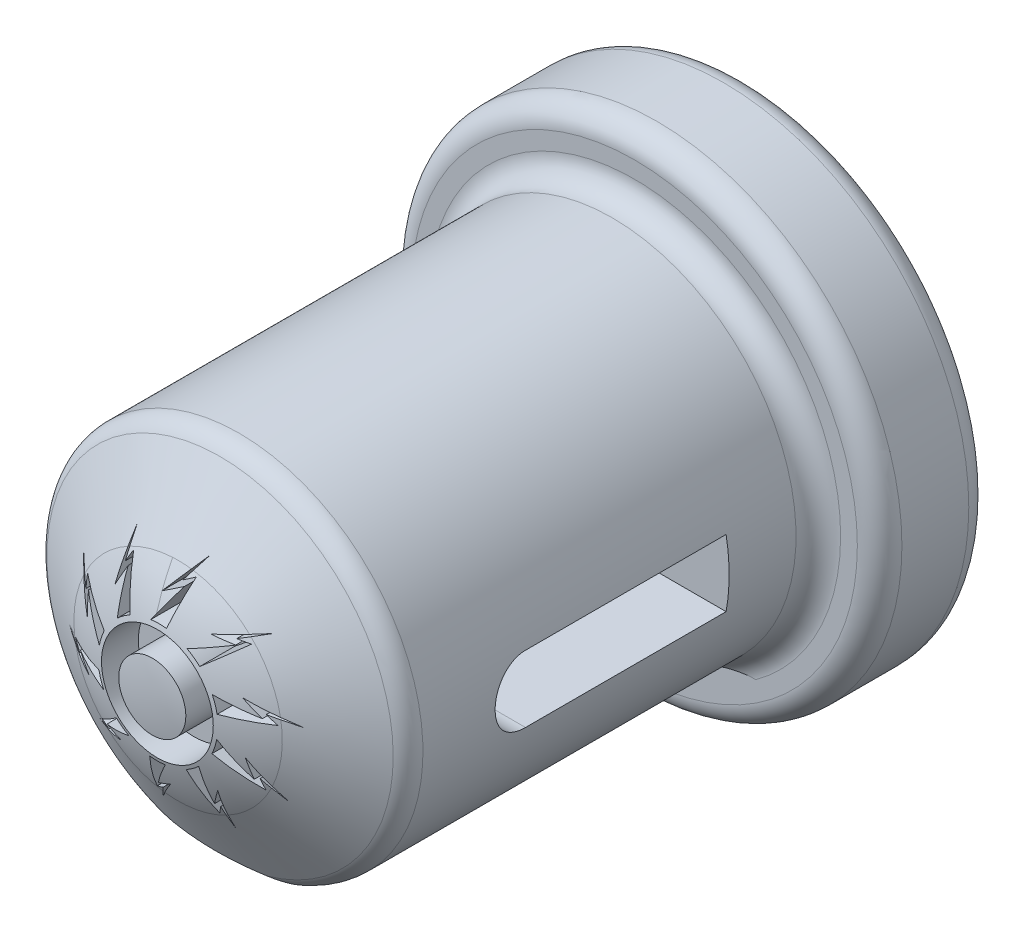
SolidWorks part; units mm, degrees
ref_plane "Alzado" through (0, 0, 0) normal (0, 0, 1) x (1, 0, 0)
ref_plane "Planta" through (0, 0, 0) normal (0, 1, 0) x (1, 0, 0)
ref_plane "Vista lateral" through (0, 0, 0) normal (1, 0, 0) x (0, 0, -1)
sketch "Croquis1" plane through (0, 0, 0) normal (0, 0, 1) x (1, 0, 0)
  line L0 (3.4971, -7.4721) -> (-3.4971, -7.4721)
  line L1 (2.75, -4.4721) -> (-2.75, -4.4721)
  arc A0 (2.75, -4.4721) -> (-2.75, -4.4721) centre (0, 0) ccw
  arc A1 (3.4971, -7.4721) -> (-3.4971, -7.4721) centre (0, 0) ccw
  point P7 (0, -4.4721)
  dimension "D1" = 10.5
  dimension "D2" = 5.5
  dimension "D3" = 3
extrude "Saliente-Extruir1" add sketch "Croquis1" along normal blind 23.3
sketch "Croquis2" plane through (0, 0, 0) normal (0, 0, -1) x (-1, 0, 0)
  line L0 (2.75, -4.4721) -> (-2.75, -4.4721) construction
  line L1 (2.75, -4.4721) -> (-2.75, -4.4721)
  circle A0 centre (0, 0) radius 11
  arc A1 (2.75, -4.4721) -> (-2.75, -4.4721) centre (0, 0) ccw construction
  arc A2 (2.75, -4.4721) -> (-2.75, -4.4721) centre (0, 0) ccw
  dimension "D1" = 22
extrude "Saliente-Extruir2" add sketch "Croquis2" against normal blind 5
sketch "Croquis3" plane through (0, 0, 0) normal (1, 0, 0) x (0, 0, -1)
  line L0 (-23.3, 0) -> (-23.3, 8.25)
  line L2 (-23.3, 8.25) -> (-25.4732, 4.6757)
  line L3 (-26.7831, 0) -> (-23.3, 0)
  arc A0 (-25.4732, 4.6757) -> (-26.7831, 0) centre (-17.7831, 0) ccw
  dimension "D2" = 9
  dimension "D1" = 31.3
revolve "Revolución1" add sketch "Croquis3" angle 360 about L3
sketch "Croquis4" plane through (0, 0, 23.3) normal (0, 0, -1) x (-1, 0, 0)
  line L1 (3.4971, -7.4721) -> (-3.4971, -7.4721)
  line L2 (3.4971, -7.4721) -> (-3.4971, -7.4721)
  arc A1 (-3.4971, -7.4721) -> (3.4971, -7.4721) centre (0, 0) ccw
  arc A2 (-3.4971, -7.4721) -> (3.4971, -7.4721) centre (0, 0) ccw
  dimension "D1" = 0
extrude "Cortar-Extruir1" cut sketch "Croquis4" against normal up to next
fillet "Redondeo3" radius 1 4 edges at (-11, 0, 0) (-11, 0, 5) (0, 8.25, 5) (0, 8.25, 23.3)
fillet "Redondeo2" radius 1 2 edges at (0, -4.4721, 0) (0, 5.25, 0)
ref_plane "Plano1" through (0, 0, 26.7831) normal (0, 0, 1) x (1, 0, 0)
sketch "Croquis5" plane through (0, 0, 26.7831) normal (0, 0, 1) x (1, 0, 0)
  line L0 (1.3026, 2.3441) -> (2.8816, 2.9738)
  line L1 (-0.324, 2.662) -> (0.5833, 4.0996)
  line L2 (0.5833, 4.0996) -> (-0.19, 3.662)
  line L3 (-0.19, 3.662) -> (1.0396, 5.192)
  line L4 (1.0396, 5.192) -> (0.4463, 4.2519)
  line L5 (0.4463, 4.2519) -> (0.876, 4.4951)
  line L6 (0.876, 4.4951) -> (0.376, 2.662)
  line L7 (2.8816, 2.9738) -> (1.9987, 3.0743)
  line L8 (1.9987, 3.0743) -> (3.8929, 3.5894)
  line L9 (3.8929, 3.5894) -> (2.8603, 3.1775)
  line L10 (2.8603, 3.1775) -> (3.3508, 3.1217)
  line L11 (3.3508, 3.1217) -> (1.8689, 1.9326)
  line L12 (2.4316, 1.1308) -> (4.0792, 0.7121)
  line L13 (4.0792, 0.7121) -> (3.4241, 1.3124)
  line L14 (3.4241, 1.3124) -> (5.2592, 0.6157)
  line L15 (5.2592, 0.6157) -> (4.1817, 0.8895)
  line L16 (4.1817, 0.8895) -> (4.5457, 0.5559)
  line L17 (4.5457, 0.5559) -> (2.6479, 0.465)
  line L18 (2.6319, -0.5144) -> (3.7187, -1.8216)
  line L19 (3.7187, -1.8216) -> (3.5415, -0.9509)
  line L20 (3.5415, -0.9509) -> (4.6166, -2.5932)
  line L21 (4.6166, -2.5932) -> (3.9059, -1.7384)
  line L22 (3.9059, -1.7384) -> (4.0044, -2.2222)
  line L23 (4.0044, -2.2222) -> (2.4155, -1.1802)
  line L24 (1.8268, -1.9632) -> (1.9378, -3.6595)
  line L25 (1.9378, -3.6595) -> (2.3062, -2.8509)
  line L26 (2.3062, -2.8509) -> (2.2107, -4.8115)
  line L27 (2.2107, -4.8115) -> (2.1381, -3.7022)
  line L28 (2.1381, -3.7022) -> (1.9334, -4.1515)
  line L29 (1.9334, -4.1515) -> (1.2605, -2.3746)
  line L30 (0.324, -2.662) -> (-0.5833, -4.0996)
  line L31 (-0.5833, -4.0996) -> (0.19, -3.662)
  line L32 (0.19, -3.662) -> (-1.0396, -5.192)
  line L33 (-1.0396, -5.192) -> (-0.4463, -4.2519)
  line L34 (-0.4463, -4.2519) -> (-0.876, -4.4951)
  line L35 (-0.876, -4.4951) -> (-0.376, -2.662)
  line L36 (-1.3026, -2.3441) -> (-2.8816, -2.9738)
  line L37 (-2.8816, -2.9738) -> (-1.9987, -3.0743)
  line L38 (-1.9987, -3.0743) -> (-3.8929, -3.5894)
  line L39 (-3.8929, -3.5894) -> (-2.8603, -3.1775)
  line L40 (-2.8603, -3.1775) -> (-3.3508, -3.1217)
  line L41 (-3.3508, -3.1217) -> (-1.8689, -1.9326)
  line L42 (-2.4316, -1.1308) -> (-4.0792, -0.7121)
  line L43 (-4.0792, -0.7121) -> (-3.4241, -1.3124)
  line L44 (-3.4241, -1.3124) -> (-5.2592, -0.6157)
  line L45 (-5.2592, -0.6157) -> (-4.1817, -0.8895)
  line L46 (-4.1817, -0.8895) -> (-4.5457, -0.5559)
  line L47 (-4.5457, -0.5559) -> (-2.6479, -0.465)
  line L48 (-2.6319, 0.5144) -> (-3.7187, 1.8216)
  line L49 (-3.7187, 1.8216) -> (-3.5415, 0.9509)
  line L50 (-3.5415, 0.9509) -> (-4.6166, 2.5932)
  line L51 (-4.6166, 2.5932) -> (-3.9059, 1.7384)
  line L52 (-3.9059, 1.7384) -> (-4.0044, 2.2222)
  line L53 (-4.0044, 2.2222) -> (-2.4155, 1.1802)
  line L54 (-1.8268, 1.9632) -> (-1.9378, 3.6595)
  line L55 (-1.9378, 3.6595) -> (-2.3062, 2.8509)
  line L56 (-2.3062, 2.8509) -> (-2.2107, 4.8115)
  line L57 (-2.2107, 4.8115) -> (-2.1381, 3.7022)
  line L58 (-2.1381, 3.7022) -> (-1.9334, 4.1515)
  line L59 (-1.9334, 4.1515) -> (-1.2605, 2.3746)
  circle A0 centre (0.026, -0.0152) radius 1.5
  circle A1 centre (0.026, -0.0152) radius 2.5
  arc A2 (0.376, 2.662) -> (-0.324, 2.662) centre (0.026, -0.0152) ccw
  arc A3 (1.8689, 1.9326) -> (1.3026, 2.3441) centre (0.0121, -0.0276) ccw
  arc A4 (2.6479, 0.465) -> (2.4316, 1.1308) centre (-0.0064, -0.0294) ccw
  arc A5 (2.4155, -1.1802) -> (2.6319, -0.5144) centre (-0.0225, -0.02) ccw
  arc A6 (1.2605, -2.3746) -> (1.8268, -1.9632) centre (-0.03, -0.003) ccw
  arc A7 (-0.376, -2.662) -> (0.324, -2.662) centre (-0.026, 0.0152) ccw
  arc A8 (-1.8689, -1.9326) -> (-1.3026, -2.3441) centre (-0.0121, 0.0276) ccw
  arc A9 (-2.6479, -0.465) -> (-2.4316, -1.1308) centre (0.0064, 0.0294) ccw
  arc A10 (-2.4155, 1.1802) -> (-2.6319, 0.5144) centre (0.0225, 0.02) ccw
  arc A11 (-1.2605, 2.3746) -> (-1.8268, 1.9632) centre (0.03, 0.003) ccw
  point P1 (0.026, 2.6848)
  point P4 (0.026, -0.0152)
  point P11 (0.026, -0.0152)
  point P38 (0.026, -0.0152)
  point P91 (0, 0)
  dimension "D1" = 3
  dimension "D12" = 2.7
  dimension "D9" = 5
  dimension "D2" = 0.2
  dimension "D3" = 1.9
  dimension "D4" = 1.7
  dimension "D5" = 0.7
  dimension "D6" = 0.5
  dimension "D7" = 1
  dimension "D8" = 2.53
  dimension "D10" = 0.566
  dimension "D11" = 0.6637
  dimension "D13" = 0.026
  dimension "D14" = 10
  dimension "D15" = 0.0064
extrude "Cortar-Extruir2" cut sketch "Croquis5" against normal blind 2
chamfer "Chaflán1" distance 0.5 angle 45 1 edges at (0, 5.25, 23.3)
ref_plane "Plano2" through (8.25, 0, 0) normal (1, 0, 0) x (0, 0, -1)
sketch "Croquis6" plane through (8.25, 0, 0) normal (1, 0, 0) x (0, 0, -1)
  line L0 (-18, 0) -> (-5, 0) construction
  line L1 (-18, 1.5) -> (-5, 1.5) construction
  line L2 (-18, -1.5) -> (-5, -1.5) construction
  line L3 (-23.3, -4.4721) -> (-23.3, 4.75) construction
  line L4 (-9, -1.5) -> (-9, 1.5)
  line L5 (-9, 1.5) -> (-18, 1.5)
  line L6 (-18, -1.5) -> (-9, -1.5)
  line L8 (-5, -7.4721) -> (-5, -8.25) construction
  arc A0 (-18, 1.5) -> (-18, -1.5) centre (-18, 0) ccw construction
  arc A1 (-5, -1.5) -> (-5, 1.5) centre (-5, 0) ccw construction
  arc A2 (-18, 1.5) -> (-18, -1.5) centre (-18, 0) ccw
  point P3 (-11.5, 0)
  point P8 (-19.5, 0)
  point P11 (-3.5, 0)
  dimension "D1" = 3
  dimension "D2" = 3.8
  dimension "D3" = 16
  dimension "D4" = 4
extrude "Cortar-Extruir3" cut sketch "Croquis6" against normal up to next
